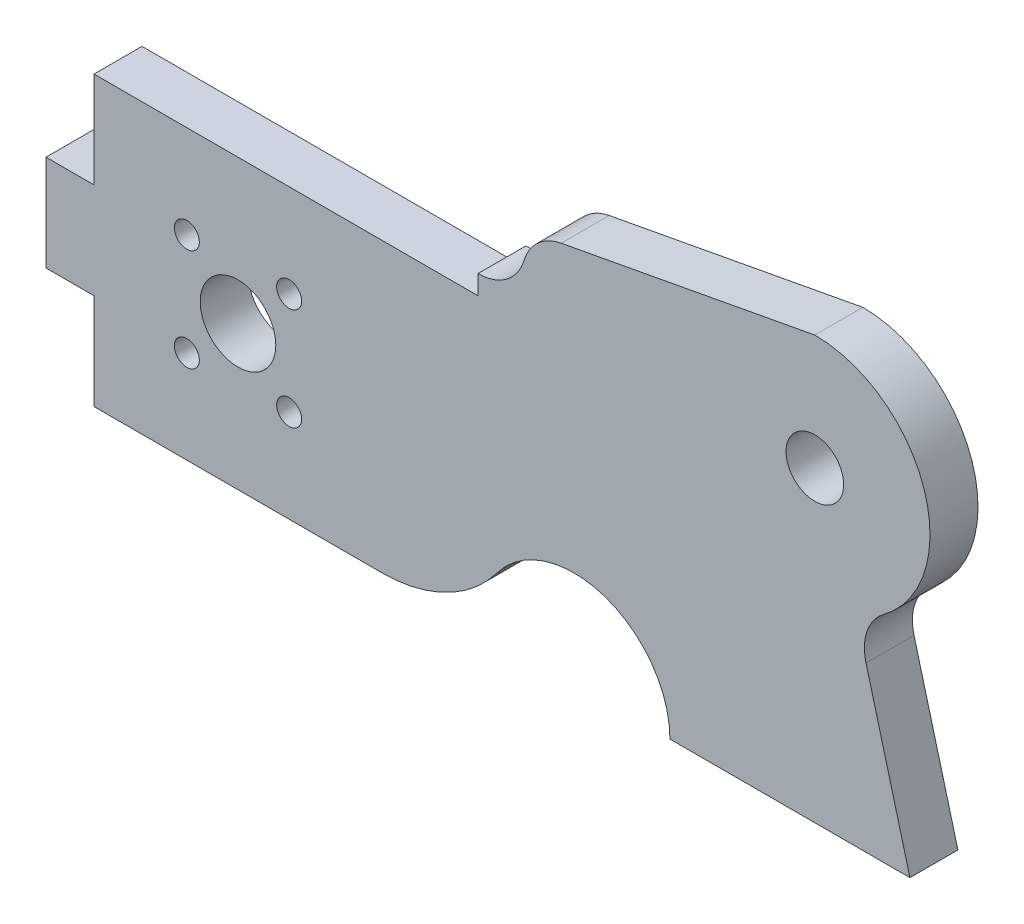
SolidWorks part; units mm, degrees
ref_plane "Front Plane" through (0, 0, 0) normal (0, 0, 1) x (1, 0, 0)
ref_plane "Top Plane" through (0, 0, 0) normal (0, 1, 0) x (1, 0, 0)
ref_plane "Right Plane" through (0, 0, 0) normal (1, 0, 0) x (0, 0, -1)
sketch "Sketch1" plane through (0, 0, 0) normal (0, 0, 1) x (1, 0, 0)
  line L0 (0, 0) -> (107.95, 0)
  line L3 (0, 38.1) -> (0, 25.4)
  line L4 (95.3675, 55.88) -> (0, 38.1)
  line L5 (0, 19.05) -> (100.2273, 19.05) construction
  line L6 (19.05, 19.05) -> (19.05, 28.62) construction
  line L7 (19.05, 19.05) -> (25.817, 25.817) construction
  line L8 (107.95, 0) -> (100.9363, 26.1756)
  line L10 (0, 12.7) -> (0, 0)
  line L11 (0, 25.4) -> (-6.35, 25.4)
  line L13 (0, 12.7) -> (-6.35, 12.7)
  line L14 (-6.35, 25.4) -> (-6.35, 12.7)
  line L15 (100.9363, 26.1756) -> (100.8688, 26.4276)
  arc A0 (100.8688, 26.4276) -> (95.3675, 55.88) centre (95.3675, 40.64) ccw
  circle A1 centre (95.3675, 40.64) radius 3.81
  circle A2 centre (19.05, 19.05) radius 9.57 construction
  circle A3 centre (25.817, 25.817) radius 1.651
  circle A4 centre (25.817, 12.283) radius 1.651
  circle A5 centre (12.283, 12.283) radius 1.651
  circle A6 centre (12.283, 25.817) radius 1.651
  point P26 (19.05, 19.05)
  dimension "D1" = 7.62
  dimension "D5" = 15.24
  dimension "D4" = 19.14
  dimension "D7" = 3.302
  dimension "D11" = 97.0107
  dimension "D2" = 38.1
  dimension "D3" = 40.64
  dimension "D6" = 107.95
  dimension "D8" = 45
  dimension "D9" = 4
  dimension "D10" = 19.05
  dimension "D12" = 75
  dimension "D14" = 12.7
  dimension "D15" = 12.7
  dimension "D16" = 6.35
extrude "Boss-Extrude1" add sketch "Sketch1" along normal blind 6.35
sketch "Sketch2" plane through (0, 0, 6.35) normal (0, 0, 1) x (1, 0, 0)
  circle A0 centre (95.3675, 40.64) radius 38.1 construction
sketch "Sketch3" plane through (0, 0, 0) normal (-1, 0, 0) x (0, 0, 1)
  line L0 (0, 38.1) -> (6.35, 25.4) construction
  line L1 (6.35, 12.7) -> (0, 0) construction
  circle A0 centre (3.175, 31.75) radius 1.5875
  circle A1 centre (3.175, 6.35) radius 1.5875
  dimension "D1" = 3.175
  dimension "D2" = 3.175
extrude "Cut-Extrude1" cut sketch "Sketch3" against normal blind 6.35
sketch "Sketch6" plane through (0, 0, 6.35) normal (0, 0, 1) x (1, 0, 0)
  line L0 (0, 0) -> (107.95, 0) construction
  line L1 (50.8, 0) -> (76.2, 0)
  arc A0 (76.2, 0) -> (50.8, 0) centre (63.5, 0) ccw
  dimension "D1" = 25.4
  dimension "D2" = 31.75
extrude "Cut-Extrude2" cut sketch "Sketch6" against normal blind 6.35
sketch "Sketch7" plane through (0, 0, 6.35) normal (0, 0, 1) x (1, 0, 0)
  line L0 (12.283, 25.817) -> (25.817, 12.283) construction
  line L1 (12.283, 12.283) -> (25.817, 25.817) construction
  circle A0 centre (19.05, 19.05) radius 5
  dimension "D1" = 10
extrude "Cut-Extrude3" cut sketch "Sketch7" against normal through all
fillet "Fillet1" radius 6.35 1 edges at (100.8688, 26.4276, 3.175)
sketch "Sketch8" plane through (0, 0, 6.35) normal (0, 0, 1) x (1, 0, 0)
  line L1 (0, 38.1) -> (50.8, 38.1)
  line L2 (0, 38.1) -> (0, 50.8)
  line L3 (0, 50.8) -> (50.8, 50.8)
  line L4 (50.8, 38.1) -> (50.8, 50.8)
  dimension "D1" = 50.8
  dimension "D2" = 12.7
extrude "Cut-Extrude4" cut sketch "Sketch8" against normal blind 50.8
sketch "Sketch9" plane through (0, 0, 6.35) normal (0, 0, 1) x (1, 0, 0)
  line L3 (50.8, 40.64) -> (57.15, 40.64)
  line L5 (57.15, 40.64) -> (50.8, 40.64)
  line L6 (57.15, 40.64) -> (57.15, 50.8)
  line L7 (57.15, 50.8) -> (50.8, 50.8)
  line L8 (50.8, 40.64) -> (50.8, 50.8)
  line L9 (0, 38.1) -> (50.8, 38.1) construction
  line M8 (50.8, 47.571) -> (50.8, 38.1)
  line M21 (95.3675, 55.88) -> (50.8, 47.571)
  dimension "D1" = 10.16
  dimension "D2" = 2.54
  dimension "D3" = 6.35
extrude "Cut-Extrude5" cut sketch "Sketch9" against normal blind 19.304 contours L3 L6 M21 M8 region at (54.0583, 44.4092, 6.35)
fillet "Fillet6" radius 6.35 1 edges at (57.15, 40.64, 3.175)
fillet "Fillet7" radius 6.35 1 edges at (57.15, 48.7549, 3.175)
fillet "Fillet8" radius 19.05 1 edges at (50.8, 0, 3.175)
